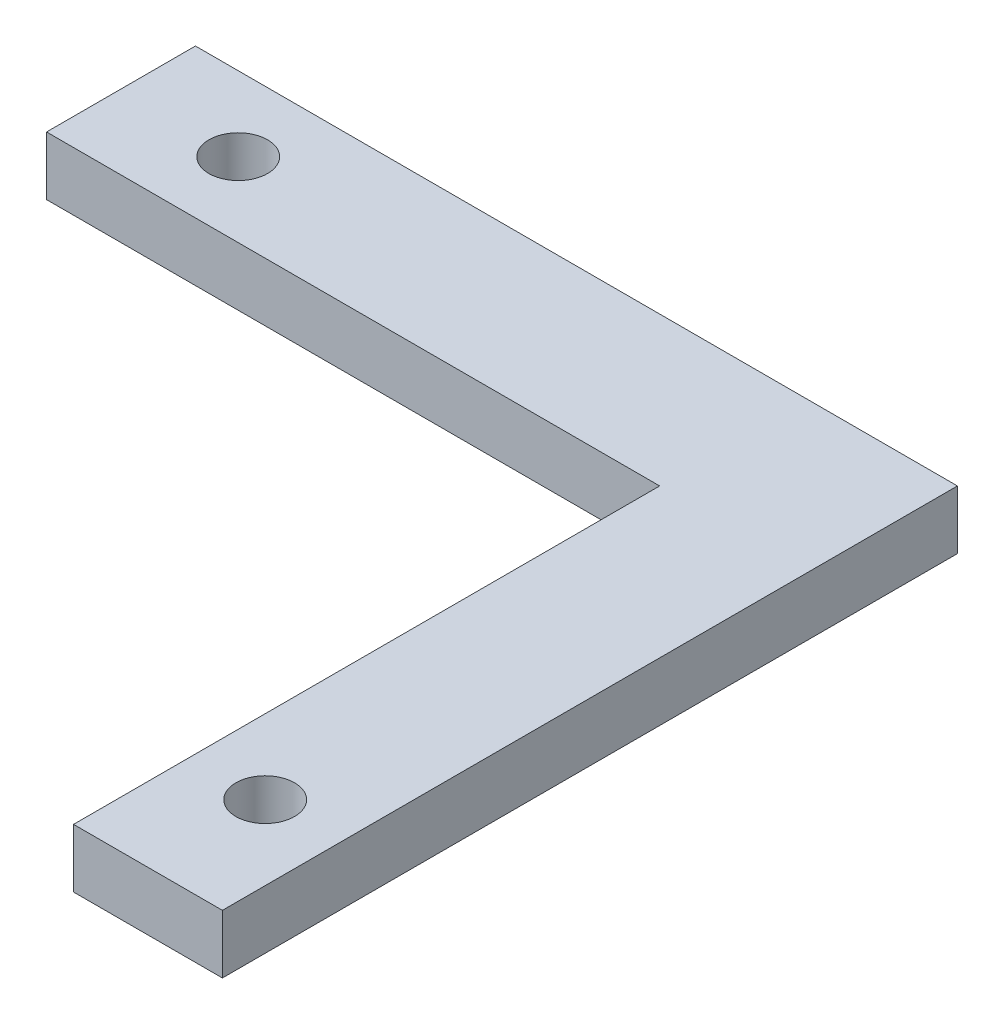
SolidWorks part; units mm, degrees
ref_plane "Front Plane" through (0, 0, 0) normal (0, 0, 1) x (1, 0, 0)
ref_plane "Top Plane" through (0, 0, 0) normal (0, 1, 0) x (1, 0, 0)
ref_plane "Right Plane" through (0, 0, 0) normal (1, 0, 0) x (0, 0, -1)
sketch "Sketch1" plane through (0, 0, 0) normal (0, 1, 0) x (1, 0, 0)
  line L0 (0, 6.35) -> (10, 6.35)
  line L2 (0, 0) -> (0, 12.7)
  line L3 (0, 12.7) -> (65, 12.7)
  line L4 (65, 0) -> (65, 12.7)
  line L5 (58.65, -50) -> (58.65, -40)
  line L7 (52.3, 0) -> (52.3, -50)
  line L8 (52.3, -50) -> (65, -50)
  line L9 (65, -50) -> (65, 0)
  line L10 (52.3, 0) -> (0, 0)
  circle A0 centre (10, 6.35) radius 2.5
  circle A2 centre (58.65, -40) radius 2.5
  dimension "D4" = 5
  dimension "D6" = 10
  dimension "D8" = 5
  dimension "D1" = 65
  dimension "D2" = 12.7
  dimension "D3" = 10
  dimension "D5" = 12.7
  dimension "D7" = 50
  dimension "D9" = 12.7
extrude "Boss-Extrude1" add sketch "Sketch1" along normal blind 5 contours L4 L3 L2 A0 region at (0.9031, 0, -9.525)
